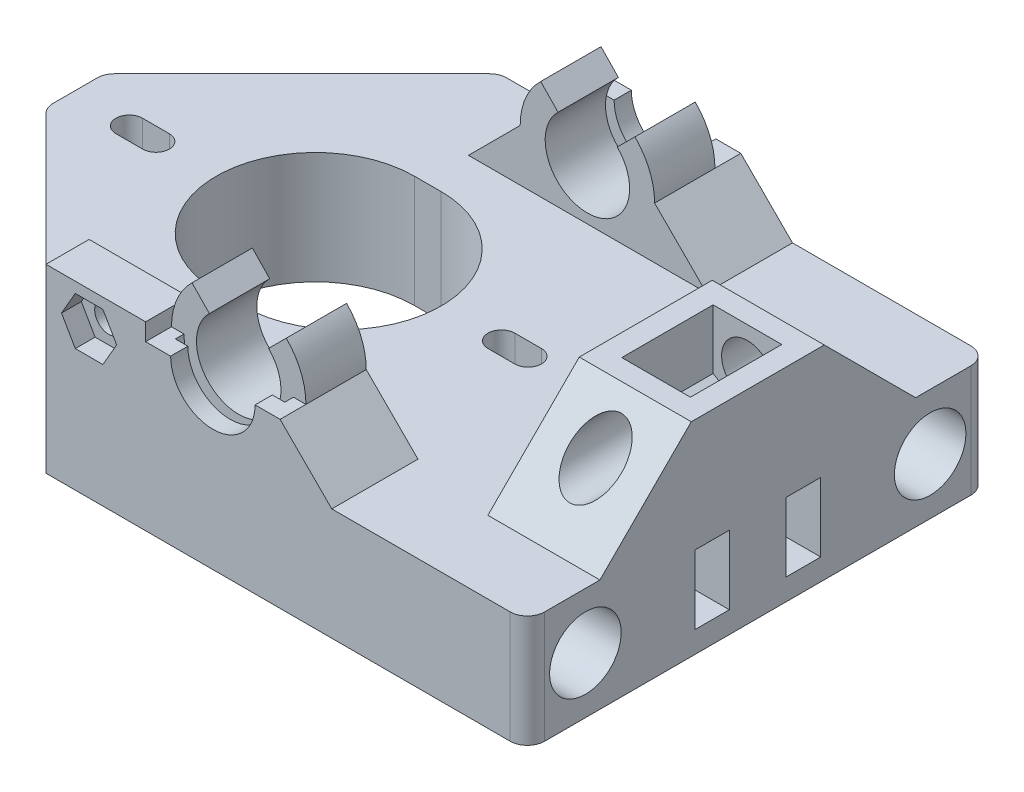
SolidWorks part; units mm, degrees
ref_plane "Front Plane" through (0, 0, 0) normal (0, 0, 1) x (1, 0, 0)
ref_plane "Top Plane" through (0, 0, 0) normal (0, 1, 0) x (1, 0, 0)
ref_plane "Right Plane" through (0, 0, 0) normal (1, 0, 0) x (0, 0, -1)
sketch "Sketch1" plane through (0, 0, 0) normal (0, 1, 0) x (1, 0, 0)
  line L0 (-23.14, -1.55) -> (-20.04, -1.55)
  line L1 (-2.9698, 26.7286) -> (-6.9063, 26.7286)
  line L2 (-23.14, 1.55) -> (-20.04, 1.55)
  line L3 (-2.9698, -26.7286) -> (-6.0698, -26.7286)
  line L4 (0, -29.6985) -> (0, -23.14) construction
  line L5 (20.04, 1.5508) -> (23.1396, 1.5515)
  line L6 (17.29, 0) -> (17.29, 33.0509)
  line L7 (17.29, 33.0509) -> (9.29, 33.0509)
  line L8 (0, 23.14) -> (0, 29.6985) construction
  line L11 (0, -20.04) -> (0, -11.5) construction
  line L12 (9.29, 33.0509) -> (9.29, -36.2665)
  line L13 (9.29, -36.2665) -> (17.29, -36.2665)
  line L15 (20.04, -1.5508) -> (23.14, -1.5515)
  line L16 (0, 0) -> (-1.55, 0) construction
  line L17 (0, 0) -> (1.55, 0) construction
  line L18 (0, 11.5) -> (0, 20.04) construction
  line L19 (0, -11.3951) -> (0, 11.3951) construction
  line L20 (-1.55, -11.5) -> (1.55, -11.5)
  line L21 (-1.55, 11.5) -> (1.55, 11.5)
  line L23 (17.29, -36.2665) -> (17.29, 0)
  line L24 (-2.9698, 26.7286) -> (2.9698, 26.7286)
  line L26 (2.9698, -26.7286) -> (-2.9698, -26.7286)
  line L27 (2.9698, -26.7286) -> (29.6985, -26.7286)
  line L28 (29.6985, -26.7286) -> (29.6985, 26.7286)
  line L29 (29.6985, 26.7286) -> (2.9698, 26.7286)
  line L30 (-29.8286, 3.8063) -> (-29.8286, -2.9698)
  line L31 (-6.0698, -26.7286) -> (-29.8286, -2.9698)
  line L32 (-6.9063, 26.7286) -> (-29.8286, 3.8063)
  circle A1 centre (0, 0) radius 2.5 construction
  arc A4 (-23.14, 1.55) -> (-23.14, -1.55) centre (-23.14, 0) ccw
  arc A5 (-1.55, 11.5) -> (-1.55, -11.5) centre (-1.55, 0) ccw
  arc A6 (20.04, 1.5508) -> (20.04, -1.5508) centre (20.0404, 0) ccw
  circle A7 centre (20.04, 0) radius 2.75 construction
  arc A9 (-20.04, -1.55) -> (-20.04, 1.55) centre (-20.04, 0) ccw
  arc A13 (21.5899, 0.0664) -> (21.5899, -0.0664) centre (23.14, 0) ccw
  arc A14 (21.5344, 1.549) -> (3.0841, 21.3686) centre (0, 0) ccw construction
  arc A15 (1.55, -11.5) -> (1.55, 11.5) centre (1.55, 0) ccw
  arc A16 (23.14, -1.5515) -> (23.1396, 1.5515) centre (23.14, 0) ccw
  arc A17 (21.5899, -0.0664) -> (21.5899, 0.0664) centre (0, 0) ccw construction
  arc A18 (21.5896, -0.0595) -> (21.5896, 0.0595) centre (20.04, 0) ccw
  dimension "D2" = 5
  dimension "D3" = 3.1
  dimension "D4" = 1.5515
  dimension "D5" = 1.55
  dimension "D6" = 1.55
  dimension "D7" = 1.55
  dimension "D9" = 8
  dimension "D10" = 20.04
  dimension "D11" = 3.1
  dimension "D12" = 18.4904
  dimension "D13" = 23
  dimension "D14" = 23
  dimension "D8" = 1.55
extrude "Boss-Extrude2" add sketch "Sketch1" along normal blind 13 contours L32 L30 L31 L3 L26 L27 L28 L29 L24 L1
extrude "Cut-Extrude6" cut sketch "Sketch1<8>" along normal through all from surface contours L0 A9 L2 A4 region at (-21.59, 0, 0) starting at face at (-2.2061, 0, -0.1394)
sketch "Sketch1<8>" plane through (0, 0, 0) normal (0, 1, 0) x (1, 0, 0) same geometry as "Sketch1"
extrude "Cut-Extrude7" cut sketch "Sketch1<9>" along normal through all contours L20 A15 L12 L21 A5 | L12 A15 region at (10.8173, 0, 0) region at (-1.082, 0, 0)
sketch "Sketch1<9>" plane through (0, 0, 0) normal (0, 1, 0) x (1, 0, 0) same geometry as "Sketch1"
extrude "Cut-Extrude8" cut sketch "Sketch1<11>" along normal blind 13 contours L15 A16 L5 A6 A18 A13 region at (21.5908, 0, 0)
sketch "Sketch1<11>" plane through (0, 0, 0) normal (0, 1, 0) x (1, 0, 0) same geometry as "Sketch1"
sketch "Sketch7" plane through (29.6985, 0, 0) normal (1, 0, 0) x (0, 0, -1)
  line L0 (-26.7286, 6.5) -> (26.7286, 6.5) construction
  line L1 (-26.7286, 13) -> (-26.7286, 0) construction
  line L2 (26.7286, 13) -> (26.7286, 0) construction
  line L3 (0, 6.5) -> (0, 28.2667) construction
  circle A0 centre (-20, 6.5) radius 4.15
  circle A1 centre (20, 6.5) radius 4.15
  dimension "D1" = 8.3
  dimension "D2" = 8.3
  dimension "D3" = 20
  dimension "D4" = 20
extrude "Cut-Extrude9" cut sketch "Sketch7" against normal blind 30
sketch "Sketch9" plane through (0, 0, 26.7286) normal (0, 0, 1) x (1, 0, 0)
  line L0 (9.29, 0) -> (17.29, 0) construction
  line L1 (9.29, 0) -> (17.29, 0)
  line L2 (13.29, 0) -> (13.29, 20) construction
  line L3 (9.8862, 22.5248) -> (7.8717, 24.6109)
  line L4 (29.6985, 13) -> (-6.0698, 13)
  line L5 (-6.0698, 13) -> (-6.0698, 0)
  line L6 (-6.0698, 0) -> (29.6985, 0)
  line L7 (29.6985, 0) -> (29.6985, 13)
  line L8 (29.6985, 13) -> (-6.0698, 13)
  line L9 (-6.0698, 13) -> (-6.0698, 0)
  line L10 (-6.0698, 0) -> (29.6985, 0)
  line L11 (29.6985, 0) -> (29.6985, 13)
  line L12 (16.7548, 22.4648) -> (18.8054, 24.5154)
  line L13 (21.09, 19) -> (27.09, 13)
  line L14 (5.49, 13) -> (21.09, 13)
  line L16 (5.49, 19) -> (-0.51, 13)
  line L17 (-0.51, 13) -> (5.49, 13)
  line L18 (27.09, 13) -> (21.09, 13)
  arc A0 (10.5114, 21.8774) -> (16.1184, 21.8284) centre (13.29, 19) ccw construction
  arc A1 (9.8862, 22.5248) -> (16.7548, 22.4648) centre (13.29, 19) ccw
  arc A2 (7.8717, 24.6109) -> (5.49, 19) centre (13.29, 19) ccw
  arc A4 (21.09, 19) -> (18.8054, 24.5154) centre (13.29, 19) ccw
  dimension "D2" = 8
  dimension "D3" = 6
  dimension "D4" = 9.8
  dimension "D5" = 15.6
  dimension "D1" = 0
extrude "Boss-Extrude3" add sketch "Sketch9" against normal blind 10 contours A1 L12 A4 L13 L18 L14 L17 L16 A2 L3
ref_plane "Plane1" through (0, 0, 24.7286) normal (0, 0, 1) x (1, 0, 0)
sketch "Sketch10" plane through (0, 0, 24.7286) normal (0, 0, 1) x (1, 0, 0)
  line L0 (6.94, 19) -> (6.94, 29.4306)
  line L1 (6.94, 29.4306) -> (19.64, 29.4306)
  line L2 (19.64, 29.4306) -> (19.64, 19)
  arc A0 (9.8862, 22.5248) -> (16.7548, 22.4648) centre (13.29, 19) ccw construction
  arc A1 (9.8862, 22.5248) -> (16.7548, 22.4648) centre (13.29, 19) ccw construction
  arc A2 (6.94, 19) -> (19.64, 19) centre (13.29, 19) ccw
  dimension "D1" = 12.7
extrude "Cut-Extrude10" cut sketch "Sketch10" against normal blind 1
ref_plane "Plane3" through (0, 0, 0) normal (0, 0, 1) x (1, 0, 0)
mirror "Mirror1" about plane through (0, 0, 0) normal (0, 0, 1) of "Boss-Extrude3", "Cut-Extrude10"
sketch "Sketch12" plane through (0, 0, 26.7286) normal (0, 0, 1) x (1, 0, 0)
  line L0 (13.29, 19) -> (43.29, 19)
  line L1 (43.29, 19) -> (49.29, 19)
  line L9 (29.6985, 13) -> (27.09, 13)
  line L10 (27.09, 13) -> (21.09, 19)
  line L11 (18.8054, 24.5154) -> (16.7548, 22.4648)
  line L12 (9.8862, 22.5248) -> (7.8717, 24.6109)
  line L13 (5.49, 19) -> (-0.51, 13)
  line L14 (-0.51, 13) -> (-6.0698, 13)
  line L15 (-6.0698, 13) -> (-6.0698, 0)
  line L16 (-6.0698, 0) -> (29.6985, 0)
  line L17 (29.6985, 0) -> (29.6985, 13)
  line L18 (29.6985, 13) -> (27.09, 13)
  line L19 (27.09, 13) -> (21.09, 19)
  line L20 (18.8054, 24.5154) -> (16.7548, 22.4648)
  line L21 (9.8862, 22.5248) -> (7.8717, 24.6109)
  line L22 (5.49, 19) -> (-0.51, 13)
  line L23 (-0.51, 13) -> (-6.0698, 13)
  line L24 (-6.0698, 13) -> (-6.0698, 0)
  line L25 (-6.0698, 0) -> (29.6985, 0)
  line L26 (29.6985, 0) -> (29.6985, 13)
  circle A0 centre (43.29, 19) radius 3
  circle A1 centre (43.29, 19) radius 4.6
  arc A3 (21.09, 19) -> (18.8054, 24.5154) centre (13.29, 19) ccw
  arc A4 (9.8862, 22.5248) -> (16.7548, 22.4648) centre (13.29, 19) ccw
  arc A5 (7.8717, 24.6109) -> (5.49, 19) centre (13.29, 19) ccw
  arc A6 (21.09, 19) -> (18.8054, 24.5154) centre (13.29, 19) ccw
  arc A7 (9.8862, 22.5248) -> (16.7548, 22.4648) centre (13.29, 19) ccw
  arc A8 (7.8717, 24.6109) -> (5.49, 19) centre (13.29, 19) ccw
  dimension "D3" = 6
  dimension "D5" = 9.2
  dimension "D2" = 30
  dimension "D4" = 6
  dimension "D1" = 0
sketch "Sketch13" plane through (29.6985, 0, 0) normal (1, 0, 0) x (0, 0, -1)
  line L4 (-26.7286, 0) -> (26.7286, 0)
  line L5 (26.7286, 0) -> (26.7286, 13)
  line L6 (26.7286, 13) -> (-26.7286, 13)
  line L7 (-26.7286, 13) -> (-26.7286, 0)
  line L8 (-26.7286, 0) -> (26.7286, 0)
  line L9 (26.7286, 0) -> (26.7286, 13)
  line L10 (26.7286, 13) -> (-26.7286, 13)
  line L11 (-26.7286, 13) -> (-26.7286, 0)
  circle A0 centre (-20, 6.5) radius 4.15 construction
  circle A1 centre (20, 6.5) radius 4.15 construction
  circle A2 centre (-20, 6.5) radius 4.15
  circle A3 centre (20, 6.5) radius 4.15
  dimension "D1" = 0
extrude "Boss-Extrude4" add sketch "Sketch13" along normal blind 20.09
sketch "Sketch17" plane through (0, 13, 0) normal (0, 1, 0) x (1, 0, 0)
  line L0 (43.29, -26.7286) -> (43.29, 26.7286) construction
  line L1 (13.29, -26.7286) -> (43.29, -26.7286) construction
  line L2 (43.29, -26.7286) -> (49.29, -26.7286) construction
  line L3 (49.7885, 26.7286) -> (27.09, 26.7286) construction
  line L4 (26.8938, 0) -> (57.56, 0) construction
  line L6 (49.79, -7.7162) -> (36.79, -7.7162)
  line L7 (49.79, -7.7162) -> (49.79, 7.7162)
  line L8 (49.79, 7.7162) -> (36.79, 7.7162)
  line L9 (36.79, -7.7162) -> (36.79, 7.7162)
  line L10 (49.79, -7.7162) -> (36.79, 7.7162) construction
  line L11 (49.79, 7.7162) -> (36.79, -7.7162) construction
  point P11 (43.29, 0)
  dimension "D1" = 13
extrude "Boss-Extrude5" add sketch "Sketch17" along normal blind 10.6
chamfer "Chamfer1" distance 10.6 angle 45 2 edges at (43.2892, 13, -7.7162) (43.2892, 13, 7.7162)
extrude "Cut-Extrude11" cut sketch "Sketch12" against normal through all contours A0
ref_plane "Plane4" through (0, 0, 6.1486) normal (0, 0, 1) x (1, 0, 0)
sketch "Sketch24" plane through (0, 0, 6.1486) normal (0, 0, 1) x (1, 0, 0)
  line L0 (39.3063, 21.3) -> (39.3063, 23.6)
  line L1 (39.3063, 21.3) -> (39.3063, 16.7)
  line L2 (39.3063, 16.7) -> (43.29, 14.4)
  line L3 (43.29, 14.4) -> (47.2737, 16.7)
  line L4 (47.2737, 16.7) -> (47.2737, 21.3)
  line L5 (39.3063, 23.6) -> (47.2737, 23.6)
  line L6 (47.2737, 23.6) -> (47.2756, 23.5831)
  line L7 (36.79, 23.6) -> (49.7885, 23.6) construction
  line L8 (39.3063, 23.6) -> (47.2737, 23.6)
  line L9 (47.2737, 23.6) -> (47.2737, 21.3)
  line L11 (43.29, 23.6) -> (39.3063, 21.3) [skipped]
  line L12 (47.2737, 21.3) -> (43.29, 23.6) [skipped]
extrude "Cut-Extrude12" cut sketch "Sketch24" against normal blind 5.3 from surface contours L9 L5 L0 L1 L2 L3 L4 region at (43.29, 19, 6.1486) region at (40.6342, 22.8333, 6.1486) region at (45.9458, 22.8333, 6.1486) starting at plane "Plane3"
fillet "Fillet2" radius 2 2 edges at (49.7885, 6.5, -26.7286) (49.7885, 6.5, 26.7286)
sketch "Sketch25" plane through (49.79, 0, 0) normal (1, 0, 0) x (0, 0, -1)
  line L1 (-43.1543, -25.6497) -> (43.1543, -25.6497)
  line L2 (-43.1543, -25.6497) -> (-43.1543, 43.4536)
  line L3 (-43.1543, 43.4536) -> (43.1543, 43.4536)
  line L4 (43.1543, -25.6497) -> (43.1543, 43.4536)
  line L5 (-43.1543, -25.6497) -> (43.1543, 43.4536) construction
  line L6 (-43.1543, 43.4536) -> (43.1543, -25.6497) construction
  point P0 (0, 8.9019)
extrude "Cut-Extrude13" cut sketch "Sketch25" against normal up to surface (0.0015 mm away) up to face at (49.7885, 6.5, 15.85)
sketch "Sketch26" plane through (0, 13, 0) normal (0, 1, 0) x (1, 0, 0)
  arc A2 (21.5896, 0.0595) -> (21.5896, -0.0595) centre (23.14, 0) ccw
  arc A3 (21.5896, -0.0595) -> (21.5896, 0.0595) centre (20.04, 0) ccw
  arc A4 (21.5896, 0.0595) -> (21.5896, -0.0595) centre (23.14, 0) ccw
  arc A5 (21.5896, -0.0595) -> (21.5896, 0.0595) centre (20.04, 0) ccw
  dimension "D1" = 0
extrude "Cut-Extrude14" cut sketch "Sketch26" against normal through all
sketch "Sketch27" plane through (49.7885, 0, 0) normal (1, 0, 0) x (0, 0, -1)
  line L0 (-20, 6.5) -> (20, 6.5) construction
  line L1 (0, 6.5) -> (-5.3, 6.5)
  line L3 (-3.3, 2.5) -> (-7.3, 2.5)
  line L4 (-3.3, 2.5) -> (-3.3, 10.5)
  line L5 (-3.3, 10.5) -> (-7.3, 10.5)
  line L6 (-7.3, 2.5) -> (-7.3, 10.5)
  line L7 (-3.3, 2.5) -> (-7.3, 10.5) construction
  line L8 (-3.3, 10.5) -> (-7.3, 2.5) construction
  circle A0 centre (-20, 6.5) radius 4.15 construction
  circle A1 centre (20, 6.5) radius 4.15 construction
  circle A2 centre (-20, 6.5) radius 4.15 construction
  circle A3 centre (20, 6.5) radius 4.15 construction
  dimension "D1" = 5.3
  dimension "D2" = 4
  dimension "D3" = 8
extrude "Cut-Extrude15" cut sketch "Sketch27" against normal up to next contours L6 L3 L4 L5 region at (49.7885, 2.5894, 5.3)
mirror "Mirror2" about plane through (0, 0, 0) normal (0, 0, 1) of "Cut-Extrude15"
mirror "Mirror3" about plane through (0, 0, 0) normal (0, 0, 1) of "Cut-Extrude12"
sketch "Sketch28" plane through (0, 0, 26.7286) normal (0, 0, 1) x (1, 0, 0)
  line L1 (5.49, 19) -> (24.7648, 19)
  line L2 (5.49, 19) -> (5.49, 27.4634)
  line L3 (5.49, 27.4634) -> (24.7648, 27.4634)
  line L4 (24.7648, 19) -> (24.7648, 27.4634)
extrude "Cut-Extrude16" cut sketch "Sketch28" against normal blind 3
mirror "Mirror4" about plane through (0, 0, 0) normal (0, 0, 1) of "Cut-Extrude16"
sketch "Sketch30" plane through (0, 13, 0) normal (0, 1, 0) x (1, 0, 0)
  line L0 (-0.51, -16.7286) -> (-0.51, -26.7286) construction
  line L1 (-4.0698, -26.7286) -> (-0.51, -26.7286)
  line L2 (-6.0698, -24.7286) -> (-6.0698, -21.7286)
  line L3 (-6.0698, -21.7286) -> (-0.51, -21.7286)
  line L4 (5.49, -16.7286) -> (5.49, -23.7286) construction
  line L5 (5.49, -23.7286) -> (5.49, -26.7286) construction
  line L6 (5.49, -21.7286) -> (5.49, -23.7286)
  line L7 (5.49, -23.7286) -> (5.49, -26.7286)
  line L8 (-0.51, -26.7286) -> (5.49, -26.7286)
  line L9 (-0.51, -21.7286) -> (5.49, -21.7286)
  line L10 (-4.0698, -26.7286) -> (-6.0698, -26.7286)
  line L11 (-6.0698, -26.7286) -> (-6.0698, -24.7286)
  point P13 (-6.0698, -26.7286)
extrude "Boss-Extrude6" add sketch "Sketch30" along normal blind 8
sketch "Sketch31" plane through (0, 0, 26.7286) normal (0, 0, 1) x (1, 0, 0)
  line L0 (-6.0698, 21) -> (-6.0698, 13) construction
  line L1 (0.5302, 19.7713) -> (-2.6698, 19.7713)
  line L2 (-2.6698, 19.7713) -> (-4.2698, 17)
  line L3 (-4.2698, 17) -> (-2.6698, 14.2287)
  line L4 (-2.6698, 14.2287) -> (0.5302, 14.2287)
  line L5 (0.5302, 14.2287) -> (2.1302, 17)
  line L6 (2.1302, 17) -> (0.5302, 19.7713)
  line L7 (-6.0698, 21) -> (5.49, 21) construction
  circle A0 centre (-1.0698, 17) radius 3.2 construction
  dimension "D1" = 6.4
  dimension "D2" = 5
  dimension "D3" = 4
extrude "Cut-Extrude17" cut sketch "Sketch31" against normal blind 2.3
sketch "Sketch32" plane through (0, 0, 24.4286) normal (0, 0, 1) x (1, 0, 0)
  line L6 (2.1302, 17) -> (0.5302, 19.7713)
  line L7 (0.5302, 19.7713) -> (-2.6698, 19.7713)
  line L8 (-2.6698, 19.7713) -> (-4.2698, 17)
  line L9 (-4.2698, 17) -> (-2.6698, 14.2287)
  line L10 (-2.6698, 14.2287) -> (0.5302, 14.2287)
  line L11 (0.5302, 14.2287) -> (2.1302, 17)
  line L12 (2.1302, 17) -> (0.5302, 19.7713) construction
  line L13 (0.5302, 19.7713) -> (-2.6698, 19.7713)
  line L14 (-2.6698, 19.7713) -> (-4.2698, 17) construction
  line L15 (-4.2698, 17) -> (-2.6698, 14.2287) construction
  line L16 (-2.6698, 14.2287) -> (0.5302, 14.2287) construction
  line L17 (0.5302, 14.2287) -> (2.1302, 17) construction
  circle A0 centre (-1.0703, 16.9489) radius 1.65
  dimension "D2" = 3.3
  dimension "D3" = 3.2
  dimension "D1" = 0
sketch "Sketch33" plane through (0, 0, 0) normal (0, -1, 0) x (1, 0, 0)
  line L0 (49.7885, 24.7286) -> (49.7885, -24.7286) construction
  circle A0 centre (46.2885, 0) radius 1.2
  dimension "D1" = 2.4
  dimension "D2" = 3.5
extrude "Cut-Extrude19" cut sketch "Sketch33" against normal blind 10
fillet "Fillet9" radius 2 3 edges at (-6.9063, 6.5, -26.7286) (-29.8286, 6.5, 2.9698) (-29.8286, 6.5, -3.8063)
extrude "Cut-Extrude20" cut sketch "Sketch32" against normal blind 10 contours A0
sketch "Sketch34" plane through (-0.3015, 0, 0) normal (1, 0, 0) x (0, 0, -1)
  circle A0 centre (-20, 6.5) radius 4.15 construction
  circle A1 centre (20, 6.5) radius 4.15 construction
  circle A2 centre (-20, 6.5) radius 4.15
  circle A3 centre (20, 6.5) radius 4.15
extrude "Boss-Extrude7" add sketch "Sketch34" along normal blind 5
